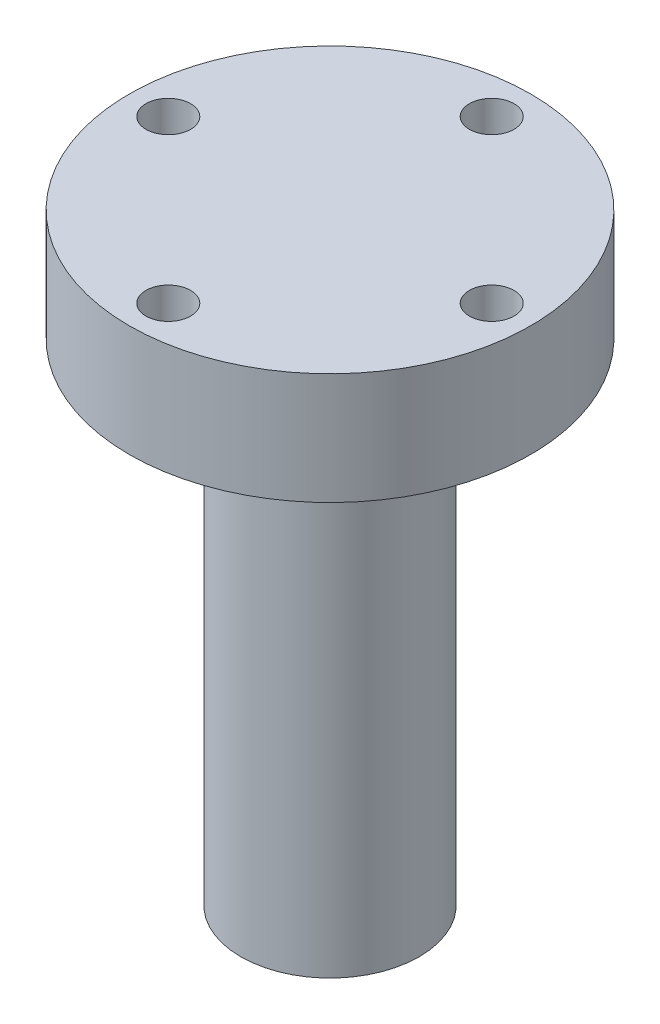
SolidWorks part; units mm, degrees
ref_plane "Front Plane" through (0, 0, 0) normal (0, 0, 1) x (1, 0, 0)
ref_plane "Top Plane" through (0, 0, 0) normal (0, 1, 0) x (1, 0, 0)
ref_plane "Right Plane" through (0, 0, 0) normal (1, 0, 0) x (0, 0, -1)
sketch "Sketch1" plane through (0, 0, 0) normal (0, 1, 0) x (1, 0, 0)
  circle A0 centre (0, 0) radius 9
  dimension "D1" = 18
extrude "BracketMount" add sketch "Sketch1" along normal blind 5
sketch "Sketch2" plane through (0, 5, 0) normal (0, 1, 0) x (1, 0, 0)
  circle A0 centre (0, 7.25) radius 1
  circle A7 centre (7.25, 0) radius 1
  circle A8 centre (0, -7.25) radius 1
  circle A9 centre (-7.25, 0) radius 1
  point P19 (0, 0)
  dimension "D1" = 2
  dimension "D3" = 7.25
  dimension "D2" = 4
extrude "Bracket-MountHoles" cut sketch "Sketch2" against normal up to surface (5 mm away) up to face at (0, 0, 9)
sketch "Sketch3" plane through (0, 0, 0) normal (0, -1, 0) x (1, 0, 0)
  circle A0 centre (0, 0) radius 4
  dimension "D1" = 8
extrude "StepperSleeve" add sketch "Sketch3" along normal blind 22
sketch "Sketch4" plane through (0, -22, 0) normal (0, -1, 0) x (1, 0, 0)
  circle A0 centre (0, 0) radius 2.6
  dimension "D1" = 5.2
extrude "InitialSeat" cut sketch "Sketch4" against normal blind 9
sketch "Sketch5" plane through (0, -13, 0) normal (0, -1, 0) x (1, 0, 0)
  line L3 (1.99, 1.5297) -> (1.99, -1.5297)
  arc A6 (1.99, 1.5297) -> (1.99, -1.5297) centre (0, 0) ccw
  point P7 (-2.51, 0)
  dimension "D1" = 4.5
extrude "OrientationNub" cut sketch "Sketch5" against normal up to surface (13 mm away) up to face at (0, 0, 4)
